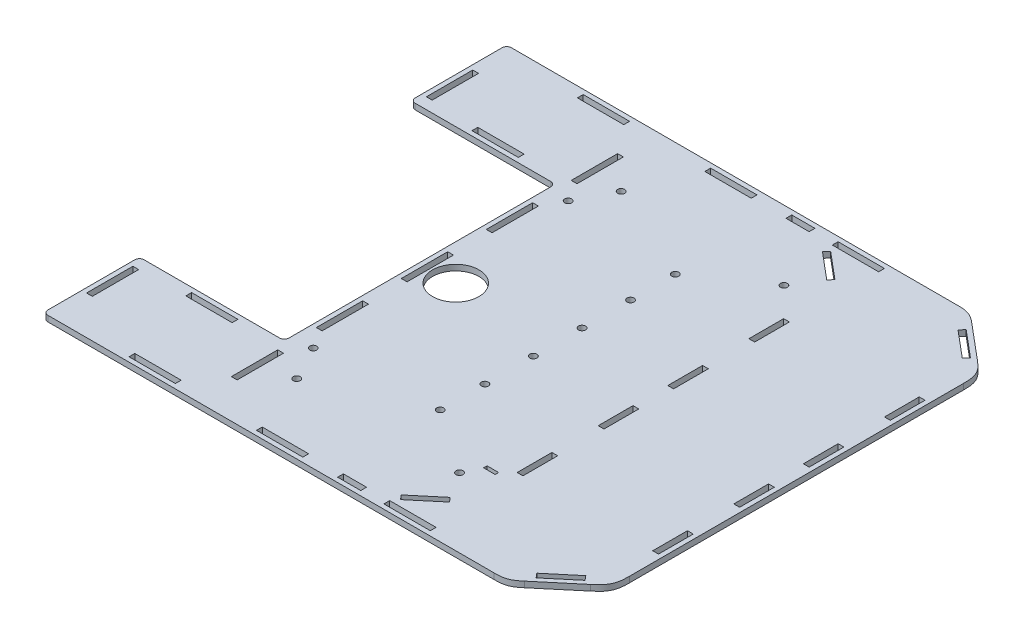
SolidWorks part; units mm, degrees
note: The reader was unsure of these and kept them because the rebuilt part matched: shared geometry of "Sketch1<3>".
material "Maple"
ref_plane "Front Plane" through (0, 0, 0) normal (0, 0, 1) x (1, 0, 0)
ref_plane "Top Plane" through (0, 0, 0) normal (0, 1, 0) x (1, 0, 0)
ref_plane "Right Plane" through (0, 0, 0) normal (1, 0, 0) x (0, 0, -1)
sketch "Sketch1" plane through (0, 0, 0) normal (0, 1, 0) x (1, 0, 0)
  line L0 (-100, -100) -> (-100, 100) construction
  line L1 (-100, -100) -> (100, -100) construction
  line L2 (-100, 0) -> (100, 0) construction
  line L3 (100, -100) -> (100, 100) construction
  line L4 (-100, -100) -> (100, 0) construction
  line L5 (-100, 0) -> (100, -100) construction
  line L6 (0, 100) -> (0, -100) construction
  line L11 (100, -100) -> (100, -65)
  line L12 (100, -65) -> (30, -65)
  line L13 (-23.5, -100) -> (-93.5, -100) construction
  line L14 (-93.5, -65) -> (-93.5, -100)
  line L15 (-23.5, -65) -> (-93.5, -65)
  line L16 (-23.5, -65) -> (-23.5, -100)
  line L17 (100, -100) -> (30, -100)
  line L18 (30, -65) -> (30, -100)
  line L19 (-93.5, -100) -> (-100, -100)
  line L23 (-100, -100) -> (-100, 100)
  line L24 (-55.5, -60.5) -> (-55.5, -63)
  line L25 (-55.5, 60.5) -> (-75.5, 60.5)
  line L26 (-93.5, -100) -> (-100, -100)
  line L32 (30, -100) -> (-23.5, -100)
  line L33 (100, 100) -> (100, 65)
  line L37 (-23.5, -100) -> (-93.5, -100)
  line L43 (10, -96.75) -> (45, -96.75) construction
  line L44 (-10, -98) -> (10, -98)
  line L45 (-10, -98) -> (-10, -95.5)
  line L46 (-10, -95.5) -> (10, -95.5)
  line L47 (10, -98) -> (10, -95.5)
  line L48 (-35.5, -83.3333) -> (-35.5, -63.3333)
  line L49 (-35.5, -83.3333) -> (-33, -83.3333)
  line L52 (-65, -98) -> (-45, -98)
  line L53 (-65, -98) -> (-65, -95.5)
  line L54 (-65, -95.5) -> (-45, -95.5)
  line L55 (-45, -98) -> (-45, -95.5)
  line L56 (45, -98) -> (65, -98)
  line L57 (-10, -96.75) -> (-45, -96.75) construction
  line L61 (100, 65) -> (30, 65)
  line L62 (30, 65) -> (30, 100)
  line L63 (100, 100) -> (30, 100)
  line L64 (30, 100) -> (-23.5, 100)
  line L65 (-96.75, -83.3333) -> (-96.75, -100) construction
  line L66 (-98, -83.3333) -> (-95.5, -83.3333)
  line L67 (-98, -83.3333) -> (-98, -63.3333)
  line L68 (-98, -63.3333) -> (-95.5, -63.3333)
  line L69 (-95.5, -83.3333) -> (-95.5, -63.3333)
  line L70 (-98, -83.3333) -> (-95.5, -63.3333) construction
  line L71 (-98, -63.3333) -> (-95.5, -83.3333) construction
  line L76 (-55.5, 60.5) -> (-55.5, 63)
  line L77 (-55.5, 63) -> (-75.5, 63)
  line L82 (-75.5, 60.5) -> (-75.5, 63)
  line L83 (-55.5, 60.5) -> (-75.5, 63) construction
  line L92 (100, -100) -> (125, -79.0225)
  line L93 (125, -79.0225) -> (125, 79.0225)
  line L98 (103.8621, -90.885) -> (115.3528, -81.2431)
  line L103 (103.8621, -90.885) -> (105.4691, -92.8001)
  line L108 (115.3528, -81.2431) -> (116.9598, -83.1583)
  line L114 (-55.5, 63) -> (-75.5, 60.5) construction
  line L115 (-55.5, -63) -> (-75.5, -63)
  line L116 (-98, 63.3333) -> (-95.5, 83.3333) construction
  line L117 (-98, 83.3333) -> (-95.5, 63.3333) construction
  line L118 (-65, -96.75) -> (-100, -96.75) construction
  line L119 (45, -98) -> (45, -95.5)
  line L120 (121.75, 77.507) -> (121.75, -77.507) construction
  line L121 (100, -95.7574) -> (121.75, -77.507) construction
  line L122 (45, -95.5) -> (65, -95.5)
  line L123 (65, -98) -> (65, -95.5)
  line L124 (45, -98) -> (65, -95.5) construction
  line L125 (45, -95.5) -> (65, -98) construction
  line L126 (100, 95.7574) -> (121.75, 77.507) construction
  line L127 (120.5, -77.507) -> (120.5, -80.9101) construction
  line L128 (115.3528, -81.2431) -> (120.213, -77.165) construction
  line L129 (120.213, -77.165) -> (121.82, -79.0801) construction
  line L130 (-75.5, -60.5) -> (-75.5, -63)
  line L131 (-55.5, -60.5) -> (-75.5, -60.5)
  line L132 (-23.5, 100) -> (-93.5, 100) construction
  line L133 (116.9598, -83.1583) -> (121.82, -79.0801) construction
  line L134 (103.8621, -90.885) -> (100, -94.1257) construction
  line L136 (-100, 0) -> (100, 100) construction
  line L137 (-100, 100) -> (100, 0) construction
  line L138 (-100, 100) -> (100, 100) construction
  line L142 (105.4691, -92.8001) -> (116.9598, -83.1583)
  line L147 (103.8621, -90.885) -> (116.9598, -83.1583) construction
  line L152 (115.3528, -81.2431) -> (105.4691, -92.8001) construction
  line L157 (110.4109, -87.0216) -> (112.5, -89.5113) construction
  line L158 (120.5, -22.507) -> (120.5, -7.507)
  line L164 (53, -41.5) -> (53, -40)
  line L165 (-37.5, -58.5) -> (-100, -58.5)
  line L170 (-95.5, 83.3333) -> (-95.5, 63.3333)
  line L171 (-98, 63.3333) -> (-95.5, 63.3333)
  line L172 (-98, 83.3333) -> (-98, 63.3333)
  line L173 (-98, 83.3333) -> (-95.5, 83.3333)
  line L174 (-96.75, 83.3333) -> (-96.75, 100) construction
  line L178 (-45, 98) -> (-45, 95.5)
  line L179 (-65, 95.5) -> (-45, 95.5)
  line L180 (-65, 98) -> (-65, 95.5)
  line L181 (-65, 98) -> (-45, 98)
  line L184 (10, 98) -> (10, 95.5)
  line L185 (-10, 95.5) -> (10, 95.5)
  line L186 (-10, 98) -> (-10, 95.5)
  line L187 (-10, 98) -> (10, 98)
  line L192 (-23.5, 100) -> (-93.5, 100)
  line L201 (-93.5, 100) -> (-100, 100)
  line L202 (-37.5, -58.5) -> (-37.5, 58.5)
  line L203 (-93.5, 100) -> (-100, 100)
  line L206 (-23.5, 65) -> (-23.5, 100)
  line L207 (-23.5, 65) -> (-93.5, 65)
  line L208 (-93.5, 65) -> (-93.5, 100)
  line L230 (120.5, -57.507) -> (123, -57.507)
  line L231 (120.5, -57.507) -> (120.5, -42.507)
  line L232 (120.5, -42.507) -> (123, -42.507)
  line L233 (123, -57.507) -> (123, -42.507)
  line L234 (120.5, -57.507) -> (123, -42.507) construction
  line L235 (120.5, -42.507) -> (123, -57.507) construction
  line L236 (120.5, -22.507) -> (123, -22.507)
  line L237 (123, -22.507) -> (123, -7.507)
  line L238 (120.5, -7.507) -> (123, -7.507)
  line L239 (100, 100) -> (125, 79.0225)
  line L240 (115.3528, 81.2431) -> (116.9598, 83.1583)
  line L241 (105.4691, 92.8001) -> (116.9598, 83.1583)
  line L242 (103.8621, 90.885) -> (105.4691, 92.8001)
  line L243 (103.8621, 90.885) -> (115.3528, 81.2431)
  line L244 (120.5, 42.507) -> (123, 42.507)
  line L245 (123, 57.507) -> (123, 42.507)
  line L246 (120.5, 57.507) -> (123, 57.507)
  line L247 (120.5, 57.507) -> (120.5, 42.507)
  line L248 (120.5, 22.507) -> (123, 22.507)
  line L249 (123, 22.507) -> (123, 7.507)
  line L250 (120.5, 7.507) -> (123, 7.507)
  line L251 (120.5, 22.507) -> (120.5, 7.507)
  line L252 (65, -96.75) -> (100, -96.75) construction
  line L268 (45.3621, -90.885) -> (41.5, -94.1257) construction
  line L269 (41.5, -100) -> (66.5, -79.0225) construction
  line L274 (-37.5, 58.5) -> (-100, 58.5)
  line L275 (-100, -58.5) -> (-100, 58.5)
  line L283 (45, 95.5) -> (65, 95.5)
  line L284 (65, 98) -> (65, 95.5)
  line L285 (45, 98) -> (65, 98)
  line L286 (45, 98) -> (45, 95.5)
  line L287 (-33, -83.3333) -> (-33, -63.3333)
  line L288 (-35.5, -63.3333) -> (-33, -63.3333)
  line L289 (-35.5, -46.6667) -> (-35.5, -26.6667)
  line L290 (-35.5, -26.6667) -> (-33, -26.6667)
  line L291 (-33, -46.6667) -> (-33, -26.6667)
  line L292 (-35.5, -46.6667) -> (-33, -46.6667)
  line L293 (-33, -10) -> (-33, 10)
  line L294 (-35.5, 10) -> (-33, 10)
  line L295 (-35.5, -10) -> (-35.5, 10)
  line L296 (-35.5, -10) -> (-33, -10)
  line L297 (-35.5, 26.6667) -> (-33, 26.6667)
  line L298 (-33, 46.6667) -> (-33, 26.6667)
  line L299 (-35.5, 46.6667) -> (-33, 46.6667)
  line L300 (-35.5, 46.6667) -> (-35.5, 26.6667)
  line L301 (-33, 83.3333) -> (-33, 63.3333)
  line L302 (-35.5, 63.3333) -> (-33, 63.3333)
  line L303 (-35.5, 83.3333) -> (-35.5, 63.3333)
  line L304 (-35.5, 83.3333) -> (-33, 83.3333)
  line L317 (41.5, 100) -> (66.5, 79.0225) construction
  line L322 (10, -95.5) -> (39.8621, -95.5) construction
  line L323 (56.8528, 81.2431) -> (58.4598, 83.1583)
  line L324 (46.9691, 92.8001) -> (58.4598, 83.1583)
  line L325 (45.3621, 90.885) -> (46.9691, 92.8001)
  line L326 (45.3621, 90.885) -> (56.8528, 81.2431)
  line L327 (41.5, -100) -> (66.5, -79.0225)
  line L328 (41.5, -94.1257) -> (39.8621, -95.5) construction
  line L329 (-37.5, -58.5) -> (-100, 58.5) construction
  line L330 (66.5, 46.4714) -> (66.5, 26.4714) construction
  line L331 (35, -95.5) -> (25, -95.5)
  line L332 (25, -98) -> (25, -95.5)
  line L333 (35, -98) -> (25, -98)
  line L334 (35, -98) -> (35, -95.5)
  line L335 (35, 98) -> (35, 95.5)
  line L336 (35, 98) -> (25, 98)
  line L337 (25, 98) -> (25, 95.5)
  line L338 (35, 95.5) -> (25, 95.5)
  line L339 (45.3621, -90.885) -> (56.8528, -81.2431)
  line L340 (56.8528, -81.2431) -> (58.4598, -83.1583)
  line L341 (46.9691, -92.8001) -> (58.4598, -83.1583)
  line L342 (45.3621, -90.885) -> (46.9691, -92.8001)
  line L343 (41.5, -95.7574) -> (63.25, -77.507) construction
  line L344 (45.3621, -90.885) -> (46.9691, -92.8001)
  line L345 (45.3621, -90.885) -> (56.8528, -81.2431)
  line L346 (56.8528, -81.2431) -> (58.4598, -83.1583)
  line L347 (46.9691, -92.8001) -> (58.4598, -83.1583)
  line L348 (64.5, 57.507) -> (64.5, 42.507)
  line L349 (62, 42.507) -> (64.5, 42.507)
  line L350 (62, 57.507) -> (62, 42.507)
  line L351 (62, 57.507) -> (64.5, 57.507)
  line L352 (62, 22.507) -> (62, 7.507)
  line L353 (62, 7.507) -> (64.5, 7.507)
  line L354 (64.5, 22.507) -> (64.5, 7.507)
  line L355 (62, 22.507) -> (64.5, 22.507)
  line L356 (62, -22.507) -> (62, -7.507)
  line L357 (62, -7.507) -> (64.5, -7.507)
  line L358 (64.5, -22.507) -> (64.5, -7.507)
  line L359 (62, -22.507) -> (64.5, -22.507)
  line L360 (62, -57.507) -> (62, -42.507)
  line L361 (62, -42.507) -> (64.5, -42.507)
  line L362 (64.5, -57.507) -> (64.5, -42.507)
  line L363 (62, -57.507) -> (64.5, -57.507)
  line L364 (56.8528, -81.2431) -> (62, -76.9241) construction
  line L365 (-37.5, 58.5) -> (-100, -58.5) construction
  line L374 (53, 61.5) -> (58, 61.5)
  line L379 (-51.5, 61.5) -> (-46.5, 61.5)
  line L380 (-51.5, -63) -> (-46.5, -63)
  line L381 (-51.5, -63) -> (-51.5, -61.5)
  line L382 (-51.5, -61.5) -> (-46.5, -61.5)
  line L383 (-46.5, -63) -> (-46.5, -61.5)
  line L384 (-46.5, 63) -> (-46.5, 61.5)
  line L385 (-51.5, 63) -> (-46.5, 63)
  line L386 (-51.5, 63) -> (-51.5, 61.5)
  line L391 (53, -63) -> (58, -63)
  line L392 (53, -63) -> (53, -61.5)
  line L393 (53, -61.5) -> (58, -61.5)
  line L394 (58, -63) -> (58, -61.5)
  line L399 (58, 63) -> (58, 61.5)
  line L400 (53, 63) -> (58, 63)
  line L401 (53, 63) -> (53, 61.5)
  line L406 (65, -65) -> (65, -42.5113) construction
  line L411 (-58.5, -65) -> (-58.5, -41.5247) construction
  line L412 (53, -41.5) -> (58, -41.5)
  line L413 (58, -41.5) -> (58, -40)
  line L414 (53, -40) -> (58, -40)
  line L415 (-51.5, -41.5) -> (-51.5, -40)
  line L416 (-51.5, -41.5) -> (-46.5, -41.5)
  line L417 (-46.5, -41.5) -> (-46.5, -40)
  line L418 (-51.5, -40) -> (-46.5, -40)
  line L419 (53, 41.5) -> (58, 41.5)
  line L420 (58, 41.5) -> (58, 40)
  line L421 (53, 40) -> (58, 40)
  line L422 (53, 41.5) -> (53, 40)
  line L423 (-51.5, 41.5) -> (-46.5, 41.5)
  line L424 (-46.5, 41.5) -> (-46.5, 40)
  line L425 (-51.5, 40) -> (-46.5, 40)
  line L426 (-51.5, 41.5) -> (-51.5, 40)
  line L427 (28, -63) -> (28, -61.5)
  line L428 (28, -63) -> (33, -63)
  line L429 (33, -63) -> (33, -61.5)
  line L430 (28, -61.5) -> (33, -61.5)
  line L431 (28, -41.5) -> (28, -40)
  line L432 (28, -40) -> (33, -40)
  line L433 (33, -41.5) -> (33, -40)
  line L434 (28, -41.5) -> (33, -41.5)
  line L435 (28, 61.5) -> (33, 61.5)
  line L436 (33, 63) -> (33, 61.5)
  line L437 (28, 63) -> (33, 63)
  line L438 (28, 63) -> (28, 61.5)
  line L439 (28, 41.5) -> (33, 41.5)
  line L440 (33, 41.5) -> (33, 40)
  line L441 (28, 40) -> (33, 40)
  line L442 (28, 41.5) -> (28, 40)
  line L443 (-26.5, -63) -> (-26.5, -61.5)
  line L444 (-26.5, -63) -> (-21.5, -63)
  line L445 (-21.5, -63) -> (-21.5, -61.5)
  line L446 (-26.5, -61.5) -> (-21.5, -61.5)
  line L447 (-26.5, -41.5) -> (-26.5, -40)
  line L448 (-26.5, -40) -> (-21.5, -40)
  line L449 (-21.5, -41.5) -> (-21.5, -40)
  line L450 (-26.5, -41.5) -> (-21.5, -41.5)
  line L451 (-26.5, 41.5) -> (-21.5, 41.5)
  line L452 (-21.5, 41.5) -> (-21.5, 40)
  line L453 (-26.5, 40) -> (-21.5, 40)
  line L454 (-26.5, 41.5) -> (-26.5, 40)
  line L455 (-26.5, 61.5) -> (-21.5, 61.5)
  line L456 (-21.5, 63) -> (-21.5, 61.5)
  line L457 (-26.5, 63) -> (-21.5, 63)
  line L458 (-26.5, 63) -> (-26.5, 61.5)
  circle A0 centre (-22, 0) radius 10
  circle A4 centre (0, 0) radius 10
  circle A22 centre (-28.5, 55) radius 1.5
  circle A23 centre (-28.5, -55) radius 1.5
  circle A24 centre (49.6238, -70) radius 1.5
  circle A25 centre (49.6238, 70) radius 1.5
  circle A34 centre (-72.5, 38.5) radius 1.5
  circle A35 centre (-52.5, 38.5) radius 1.5
  circle A36 centre (-20.6305, 70) radius 1.5 construction
  circle A37 centre (-20.6305, 70) radius 1.5
  circle A38 centre (-20.6305, -70) radius 1.5 construction
  circle A39 centre (-20.6305, -70) radius 1.5
  circle A40 centre (-62.5, -38.5) radius 4
  circle A41 centre (-62.5, 38.5) radius 4
  circle A42 centre (-72.5, -38.5) radius 1.5
  circle A43 centre (-52.5, -38.5) radius 1.5
  point P1 (0, -50)
  point P17 (-65.5, 61.75)
  point P23 (55, -96.75)
  point P50 (116.1563, -82.2007)
  point P51 (104.6656, -91.8425)
  point P61 (-96.75, -73.3333)
  point P71 (-68.75, 0)
  point P73 (110.4109, -87.0216)
  point P85 (112.5, -89.5113)
  point P86 (121.75, -50.007)
  point P99 (125, 0)
  point P157 (0, 0)
  point P206 (-96.75, 73.3333)
  point P211 (0, 50)
  dimension "D7" = 25
  dimension "D19" = 20
  dimension "D52" = 2
  dimension "D64" = 20
  dimension "D58" = 8
  dimension "D3" = 130
  dimension "D5" = 100
  dimension "D6" = 225
  dimension "D8" = 2.5
  dimension "D9" = 2
  dimension "D10" = 2.5
  dimension "D11" = 200
  dimension "D12" = 26.3862
  dimension "D13" = 20
  dimension "D14" = 35
  dimension "D15" = 195.5
  dimension "D16" = 2
  dimension "D17" = 20
  dimension "D18" = 2
  dimension "D20" = 2.5
  dimension "D23" = 2
  dimension "D24" = 2
  dimension "D26" = 60
  dimension "D27" = 2
  dimension "D28" = 2
  dimension "D22" = 15
  dimension "D25" = 20
  dimension "D29" = 20
  dimension "D30" = 70
  dimension "D31" = 35
  dimension "D32" = 6.5
  dimension "D33" = 95
  dimension "D36" = 15
  dimension "D37" = 10
  dimension "D38" = 2
  dimension "D39" = 11
  dimension "D40" = 25
  dimension "D41" = 65
  dimension "D42" = 53.5
  dimension "D21" = 16.6667
  dimension "D43" = 16.6667
  dimension "D44" = 16.6667
  dimension "D45" = 16.6667
  dimension "D46" = 2
  dimension "D47" = 60
  dimension "D48" = 30
  dimension "D49" = 39.5
  dimension "D50" = 62.5
  dimension "D51" = 2
  dimension "D53" = 7
  dimension "D54" = 5
  dimension "D55" = 1.5
  dimension "D56" = 2
  dimension "D57" = 20
  dimension "D59" = 20
  dimension "D60" = 25
  dimension "D61" = 2
  dimension "D62" = 20
  dimension "D63" = 2
  dimension "D65" = 7
  dimension "D66" = 2
  dimension "D67" = 20
  dimension "D68" = 10
  dimension "D69" = 10
  dimension "D90" = 45
  dimension "D91" = 4.5
  dimension "D34" = 2
  dimension "D35" = 2
extrude "Boss-Extrude1" [suppressed] add sketch "Sketch1" along normal mid plane 2.5
fillet "Fillet1" [suppressed] radius 2
fillet "Fillet2" [suppressed] radius 15
extrude "Boss-Extrude2" add sketch "Sketch1<3>" along normal blind 2.5
sketch "Sketch1<3>" plane through (0, 0, 0) normal (0, 1, 0) x (1, 0, 0) same geometry as "Sketch1"
fillet "Fillet3" radius 2 6 edges at (-100, 1.25, -100) (-100, 1.25, 100) (-37.5, 1.25, -58.5) (-100, 1.25, -58.5) (-37.5, 1.25, 58.5) (-100, 1.25, 58.5)
fillet "Fillet4" radius 15 4 edges at (125, 1.25, -79.0225) (100, 1.25, -100) (125, 1.25, 79.0225) (100, 1.25, 100)
hole_wizard "Ø3.0mm Dowel Hole1" positions "Sketch2" profile "Sketch3" hole size "Ø3.0" standard "ANSI Metric" end condition through all
sketch "Sketch2" plane through (0, 2.5, 0) normal (0, 1, 0) x (1, 0, 0)
  line L2 (62, 22.507) -> (62, 7.507) construction
  point P2 (22, 50.71)
  point P4 (22, 31.41)
  point P10 (22, 10.5)
  point P12 (22, -10.5)
  point P14 (22, -31.41)
  point P16 (22, -50.71)
  dimension "D1" = 19.3
  dimension "D2" = 21
  dimension "D3" = 19.3
  dimension "D4" = 20.91
  dimension "D5" = 20.91
  dimension "D6" = 10.5
  dimension "D7" = 40
sketch "Sketch3" plane through (22, 2.5, -50.71) normal (1, 0, 0) x (0, 0, 1)
  line L0 (0, 0) -> (0, 2.55)
  line L1 (0, 2.55) -> (1.5, 2.55)
  line L2 (1.5, 2.55) -> (1.5, 0)
  line L5 (1.5, 0) -> (0, 0)
  line L11 (0, -6.35) -> (0, 107.95) construction
  dimension "Thru Hole Dia." = 3
  dimension "Thru Hole Depth" = 2.55
